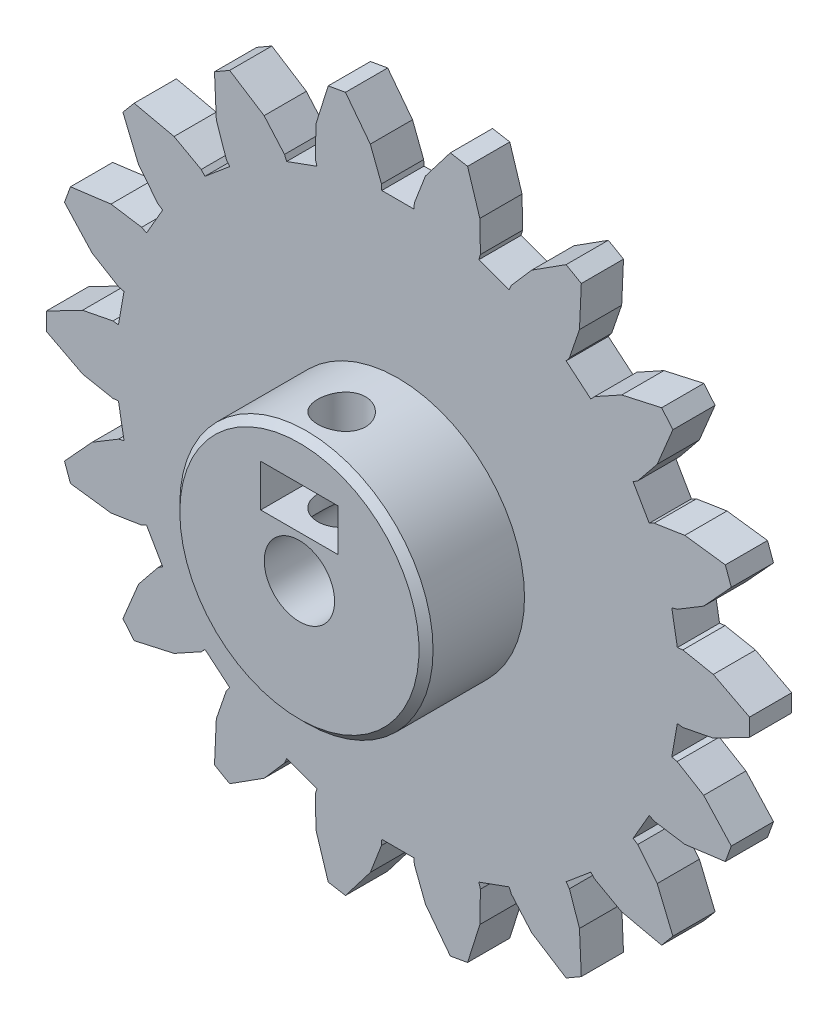
SolidWorks part; units mm, degrees
material "ABS"
ref_plane "Front Plane" through (0, 0, 0) normal (0, 0, 1) x (1, 0, 0)
ref_plane "Top Plane" through (0, 0, 0) normal (0, 1, 0) x (1, 0, 0)
ref_plane "Right Plane" through (0, 0, 0) normal (1, 0, 0) x (0, 0, -1)
sketch "Sketch1" plane through (0, 0, 0) normal (0, 0, 1) x (1, 0, 0)
  line L0 (47.7625, 28.9478) -> (48.1516, 28.9935)
  line L1 (48.1516, 28.9935) -> (50.3142, 28.5692)
  line L2 (50.3142, 28.5692) -> (52.8918, 27.2307)
  line L3 (52.8918, 27.2307) -> (52.8918, 25.9859)
  line L4 (52.8918, 25.9859) -> (50.3142, 24.6474)
  line L5 (50.3142, 24.6474) -> (48.1516, 24.2231)
  line L6 (48.1516, 24.2231) -> (47.7625, 24.2688)
  line L7 (47.7625, 24.2688) -> (47.3647, 22.0134)
  line L8 (47.3647, 22.0134) -> (47.7462, 21.9233)
  line L9 (47.7462, 21.9233) -> (49.6331, 20.785)
  line L10 (49.6331, 20.785) -> (51.5977, 18.6455)
  line L11 (51.5977, 18.6455) -> (51.1718, 17.4756)
  line L12 (51.1718, 17.4756) -> (48.2916, 17.0996)
  line L13 (48.2916, 17.0996) -> (46.1145, 17.4405)
  line L14 (46.1145, 17.4405) -> (45.7645, 17.6166)
  line L15 (45.7645, 17.6166) -> (44.6194, 15.6331)
  line L16 (44.6194, 15.6331) -> (44.9469, 15.4181)
  line L17 (44.9469, 15.4181) -> (46.3307, 13.703)
  line L18 (46.3307, 13.703) -> (47.4452, 11.0207)
  line L19 (47.4452, 11.0207) -> (46.6449, 10.0669)
  line L20 (46.6449, 10.0669) -> (43.8096, 10.6987)
  line L21 (43.8096, 10.6987) -> (41.8805, 11.7635)
  line L22 (41.8805, 11.7635) -> (41.6117, 12.0488)
  line L23 (41.6117, 12.0488) -> (39.8572, 10.5766)
  line L24 (39.8572, 10.5766) -> (40.0916, 10.2624)
  line L25 (40.0916, 10.2624) -> (40.8053, 8.1776)
  line L26 (40.8053, 8.1776) -> (40.9351, 5.276)
  line L27 (40.9351, 5.276) -> (39.857, 4.6534)
  line L28 (39.857, 4.6534) -> (37.4087, 6.2167)
  line L29 (37.4087, 6.2167) -> (35.9601, 7.8772)
  line L30 (35.9601, 7.8772) -> (35.8052, 8.2373)
  line L31 (35.8052, 8.2373) -> (33.653, 7.4539)
  line L32 (33.653, 7.4539) -> (33.7657, 7.0785)
  line L33 (33.7657, 7.0785) -> (33.7233, 4.8753)
  line L34 (33.7233, 4.8753) -> (32.8529, 2.1042)
  line L35 (32.8529, 2.1042) -> (31.6267, 1.8881)
  line L36 (31.6267, 1.8881) -> (29.861, 4.1942)
  line L37 (29.861, 4.1942) -> (29.0677, 6.2501)
  line L38 (29.0677, 6.2501) -> (29.0452, 6.6414)
  line L39 (29.0452, 6.6414) -> (26.755, 6.6414)
  line L40 (26.755, 6.6414) -> (26.7324, 6.2501)
  line L41 (26.7324, 6.2501) -> (25.9392, 4.1942)
  line L42 (25.9392, 4.1942) -> (24.1734, 1.8881)
  line L43 (24.1734, 1.8881) -> (22.9472, 2.1042)
  line L44 (22.9472, 2.1042) -> (22.0768, 4.8753)
  line L45 (22.0768, 4.8753) -> (22.0344, 7.0785)
  line L46 (22.0344, 7.0785) -> (22.1471, 7.4539)
  line L47 (22.1471, 7.4539) -> (19.995, 8.2373)
  line L48 (19.995, 8.2373) -> (19.84, 7.8772)
  line L49 (19.84, 7.8772) -> (18.3914, 6.2167)
  line L50 (18.3914, 6.2167) -> (15.9432, 4.6534)
  line L51 (15.9432, 4.6534) -> (14.865, 5.276)
  line L52 (14.865, 5.276) -> (14.9948, 8.1776)
  line L53 (14.9948, 8.1776) -> (15.7085, 10.2624)
  line L54 (15.7085, 10.2624) -> (15.943, 10.5766)
  line L55 (15.943, 10.5766) -> (14.1884, 12.0488)
  line L56 (14.1884, 12.0488) -> (13.9196, 11.7635)
  line L57 (13.9196, 11.7635) -> (11.9905, 10.6987)
  line L58 (11.9905, 10.6987) -> (9.1553, 10.0669)
  line L59 (9.1553, 10.0669) -> (8.355, 11.0207)
  line L60 (8.355, 11.0207) -> (9.4694, 13.703)
  line L61 (9.4694, 13.703) -> (10.8533, 15.4181)
  line L62 (10.8533, 15.4181) -> (11.1808, 15.6331)
  line L63 (11.1808, 15.6331) -> (10.0357, 17.6166)
  line L64 (10.0357, 17.6166) -> (9.6856, 17.4405)
  line L65 (9.6856, 17.4405) -> (7.5085, 17.0996)
  line L66 (7.5085, 17.0996) -> (4.6283, 17.4756)
  line L67 (4.6283, 17.4756) -> (4.2024, 18.6455)
  line L68 (4.2024, 18.6455) -> (6.1671, 20.785)
  line L69 (6.1671, 20.785) -> (8.054, 21.9233)
  line L70 (8.054, 21.9233) -> (8.4355, 22.0134)
  line L71 (8.4355, 22.0134) -> (8.0377, 24.2688)
  line L72 (8.0377, 24.2688) -> (7.6485, 24.2231)
  line L73 (7.6485, 24.2231) -> (5.4859, 24.6474)
  line L74 (5.4859, 24.6474) -> (2.9083, 25.9859)
  line L75 (2.9083, 25.9859) -> (2.9083, 27.2307)
  line L76 (2.9083, 27.2307) -> (5.4859, 28.5692)
  line L77 (5.4859, 28.5692) -> (7.6485, 28.9935)
  line L78 (7.6485, 28.9935) -> (8.0377, 28.9478)
  line L79 (8.0377, 28.9478) -> (8.4355, 31.2032)
  line L80 (8.4355, 31.2032) -> (8.054, 31.2933)
  line L81 (8.054, 31.2933) -> (6.1671, 32.4315)
  line L82 (6.1671, 32.4315) -> (4.2024, 34.5711)
  line L83 (4.2024, 34.5711) -> (4.6283, 35.741)
  line L84 (4.6283, 35.741) -> (7.5085, 36.117)
  line L85 (7.5085, 36.117) -> (9.6856, 35.7761)
  line L86 (9.6856, 35.7761) -> (10.0357, 35.6)
  line L87 (10.0357, 35.6) -> (11.1808, 37.5835)
  line L88 (11.1808, 37.5835) -> (10.8533, 37.7985)
  line L89 (10.8533, 37.7985) -> (9.4694, 39.5136)
  line L90 (9.4694, 39.5136) -> (8.355, 42.1959)
  line L91 (8.355, 42.1959) -> (9.1553, 43.1497)
  line L92 (9.1553, 43.1497) -> (11.9905, 42.5179)
  line L93 (11.9905, 42.5179) -> (13.9196, 41.4531)
  line L94 (13.9196, 41.4531) -> (14.1884, 41.1678)
  line L95 (14.1884, 41.1678) -> (15.943, 42.64)
  line L96 (15.943, 42.64) -> (15.7085, 42.9541)
  line L97 (15.7085, 42.9541) -> (14.9948, 45.0389)
  line L98 (14.9948, 45.0389) -> (14.865, 47.9406)
  line L99 (14.865, 47.9406) -> (15.9432, 48.5632)
  line L100 (15.9432, 48.5632) -> (18.3914, 46.9999)
  line L101 (18.3914, 46.9999) -> (19.84, 45.3394)
  line L102 (19.84, 45.3394) -> (19.995, 44.9793)
  line L103 (19.995, 44.9793) -> (22.1471, 45.7627)
  line L104 (22.1471, 45.7627) -> (22.0344, 46.1381)
  line L105 (22.0344, 46.1381) -> (22.0768, 48.3413)
  line L106 (22.0768, 48.3413) -> (22.9472, 51.1123)
  line L107 (22.9472, 51.1123) -> (24.1734, 51.3285)
  line L108 (24.1734, 51.3285) -> (25.9392, 49.0224)
  line L109 (25.9392, 49.0224) -> (26.7324, 46.9665)
  line L110 (26.7324, 46.9665) -> (26.755, 46.5752)
  line L111 (26.755, 46.5752) -> (29.0452, 46.5752)
  line L112 (29.0452, 46.5752) -> (29.0677, 46.9665)
  line L113 (29.0677, 46.9665) -> (29.861, 49.0224)
  line L114 (29.861, 49.0224) -> (31.6267, 51.3285)
  line L115 (31.6267, 51.3285) -> (32.8529, 51.1123)
  line L116 (32.8529, 51.1123) -> (33.7233, 48.3413)
  line L117 (33.7233, 48.3413) -> (33.7657, 46.1381)
  line L118 (33.7657, 46.1381) -> (33.653, 45.7627)
  line L119 (33.653, 45.7627) -> (35.8052, 44.9793)
  line L120 (35.8052, 44.9793) -> (35.9601, 45.3394)
  line L121 (35.9601, 45.3394) -> (37.4087, 46.9999)
  line L122 (37.4087, 46.9999) -> (39.857, 48.5632)
  line L123 (39.857, 48.5632) -> (40.9351, 47.9406)
  line L124 (40.9351, 47.9406) -> (40.8053, 45.0389)
  line L125 (40.8053, 45.0389) -> (40.0916, 42.9541)
  line L126 (40.0916, 42.9541) -> (39.8572, 42.64)
  line L127 (39.8572, 42.64) -> (41.6117, 41.1678)
  line L128 (41.6117, 41.1678) -> (41.8805, 41.4531)
  line L129 (41.8805, 41.4531) -> (43.8096, 42.5179)
  line L130 (43.8096, 42.5179) -> (46.6449, 43.1497)
  line L131 (46.6449, 43.1497) -> (47.4452, 42.1959)
  line L132 (47.4452, 42.1959) -> (46.3307, 39.5136)
  line L133 (46.3307, 39.5136) -> (44.9469, 37.7985)
  line L134 (44.9469, 37.7985) -> (44.6194, 37.5835)
  line L135 (44.6194, 37.5835) -> (45.7645, 35.6)
  line L136 (45.7645, 35.6) -> (46.1145, 35.7761)
  line L137 (46.1145, 35.7761) -> (48.2916, 36.117)
  line L138 (48.2916, 36.117) -> (51.1718, 35.741)
  line L139 (51.1718, 35.741) -> (51.5977, 34.5711)
  line L140 (51.5977, 34.5711) -> (49.6331, 32.4315)
  line L141 (49.6331, 32.4315) -> (47.7462, 31.2933)
  line L142 (47.7462, 31.2933) -> (47.3647, 31.2032)
  line L143 (47.3647, 31.2032) -> (47.7625, 28.9478)
  line L144 (27.9001, 46.5752) -> (27.9001, 6.6414) construction
  line L145 (52.8918, 26.6083) -> (2.9083, 26.6083) construction
sketch "Sketch2" plane through (0, 0, 0) normal (0, 0, 1) x (1, 0, 0)
  line L0 (27.9001, 46.5752) -> (27.9001, 6.6414) construction
  line L1 (52.8918, 26.6083) -> (2.9083, 26.6083) construction
  circle A0 centre (27.9001, 26.6083) radius 9
  point P0 (27.9001, 26.6083)
  dimension "D1" = 18
sketch "Sketch3" plane through (0, 0, 0) normal (0, 0, 1) x (1, 0, 0)
  circle A0 centre (27.9001, 26.6083) radius 2.5
  dimension "D1" = 5
extrude "Boss-Extrude1" add sketch "Sketch1" along normal blind 3
extrude "Boss-Extrude2" add sketch "Sketch2" along normal offset from surface (10 mm away) 7 up to face at (27.9001, 26.6083, 3) offset beyond the face yes
extrude "Cut-Extrude1" cut sketch "Sketch3" along normal through all
ref_axis "Axis1" through (27.9001, 26.6083, 10) along (0, 0, -1)
ref_plane "Plane1" through (0, 26.6083, 0) normal (0, 1, 0) x (1, 0, 0)
sketch "Sketch4" plane through (0, 26.6083, 0) normal (0, 1, 0) x (1, 0, 0)
  line L0 (27.9001, -10) -> (27.9001, 0) construction
  line L1 (18.9001, -10) -> (36.9001, -10) construction
  circle A0 centre (27.9001, -7) radius 1.7
  dimension "D1" = 3.4
  dimension "D2" = 3
extrude "Cut-Extrude2" cut sketch "Sketch4" along normal through all
sketch "Sketch6" plane through (0, 0, 10) normal (0, 0, 1) x (1, 0, 0)
  line L0 (27.9001, 35.6083) -> (27.9001, 17.6083) construction
  line L2 (25.1501, 32.6083) -> (30.6501, 32.6083)
  line L3 (25.1501, 32.6083) -> (25.1501, 29.6083)
  line L4 (25.1501, 29.6083) -> (30.6501, 29.6083)
  line L5 (30.6501, 32.6083) -> (30.6501, 29.6083)
  line L6 (25.1501, 32.6083) -> (30.6501, 29.6083) construction
  line L7 (25.1501, 29.6083) -> (30.6501, 32.6083) construction
  circle A0 centre (27.9001, 26.6083) radius 9 construction
  circle A1 centre (27.9001, 26.6083) radius 9 construction
  point P7 (27.9001, 31.1083)
  point P12 (27.9001, 26.6083)
  dimension "D1" = 5.5
  dimension "D2" = 3
  dimension "D3" = 4.5
extrude "Cut-Extrude3" cut sketch "Sketch6" against normal blind 6
chamfer "Chamfer1" distance 0.5 angle 45 1 edges at (18.9001, 26.6083, 10)
ref_axis "Axis2" through (27.9001, 26.6083, 10) along (0, 0, -1)
